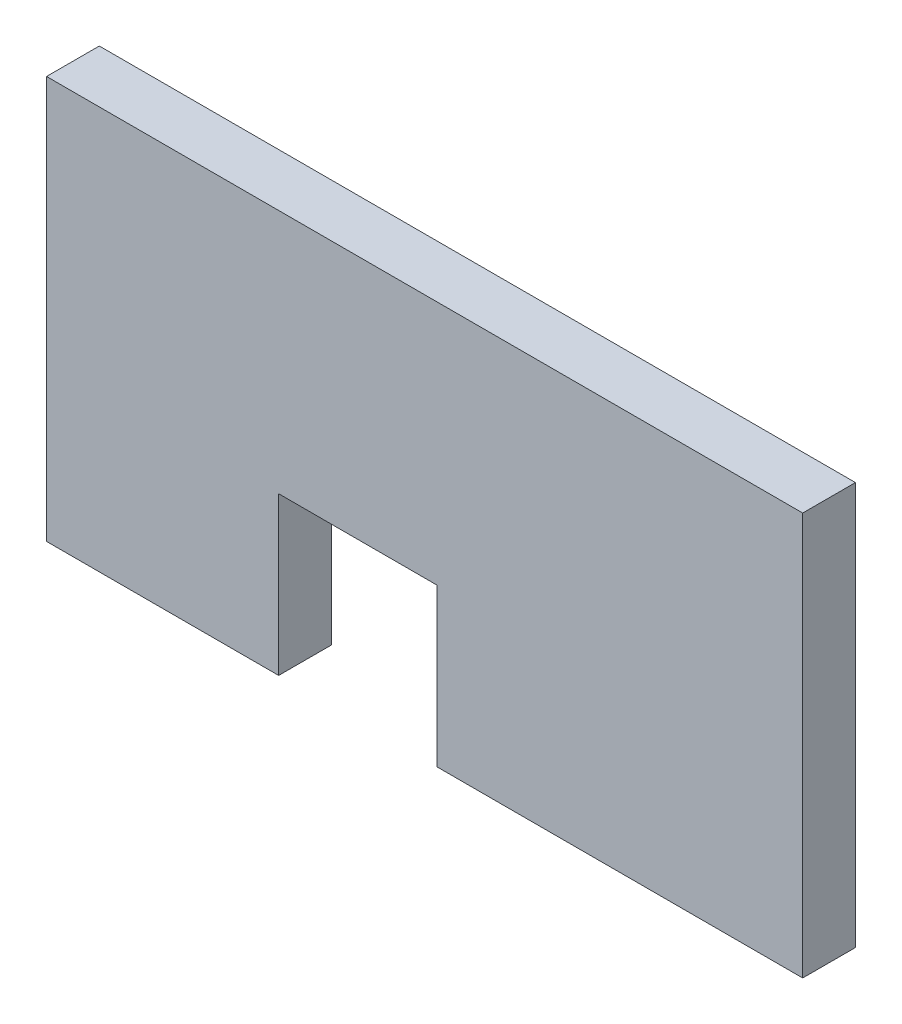
SolidWorks part; units mm, degrees
ref_plane "Front Plane" through (0, 0, 0) normal (0, 0, 1) x (1, 0, 0)
ref_plane "Top Plane" through (0, 0, 0) normal (0, 1, 0) x (1, 0, 0)
ref_plane "Right Plane" through (0, 0, 0) normal (1, 0, 0) x (0, 0, -1)
sketch "Sketch1" plane through (0, 0, 0) normal (0, 0, 1) x (1, 0, 0)
  line L0 (21.5, 33.35) -> (21.5, 15.05) construction
  line L1 (21.5, 37.95) -> (-21.5, 37.95)
  line L2 (21.5, 37.95) -> (21.5, 15.05)
  line L3 (21.5, 15.05) -> (0.7, 15.05)
  line L4 (-21.5, 37.95) -> (-21.5, 15.05)
  line L5 (-21.5, 33.35) -> (-21.5, 15.05) construction
  line L6 (32.157, 37.95) -> (-32.157, 37.95) construction
  line L7 (28.5, 15.05) -> (-28.5, 15.05) construction
  line L8 (0.7, 15.05) -> (0.7, 24) construction
  line L9 (0.7, 24) -> (-8.3, 24) construction
  line L10 (-8.3, 24) -> (-8.3, 15.05) construction
  line L11 (0.7, 15.05) -> (0.7, 24)
  line L12 (0.7, 24) -> (-8.3, 24)
  line L13 (-8.3, 24) -> (-8.3, 15.05)
  line L14 (-8.3, 15.05) -> (-21.5, 15.05)
sketch "Sketch2" plane through (0, 0, 0) normal (1, 0, 0) x (0, 0, -1)
  line L0 (0, 19.65) -> (0, 37.95) construction
  line L1 (0, 37.95) -> (-3, 37.95)
  line L2 (0, 37.95) -> (0, 15.05)
  line L3 (0, 15.05) -> (-3, 15.05)
  line L4 (-3, 37.95) -> (-3, 15.05)
  line L5 (-3, 19.65) -> (-3, 34.95) construction
  line L6 (-53.657, 15.05) -> (10.657, 15.05) construction
  line L7 (-50, 37.95) -> (7, 37.95) construction
extrude "Boss-Extrude1" add sketch "Sketch1" along normal up to vertex (3 mm away) up to point (0, 37.95, 3)
